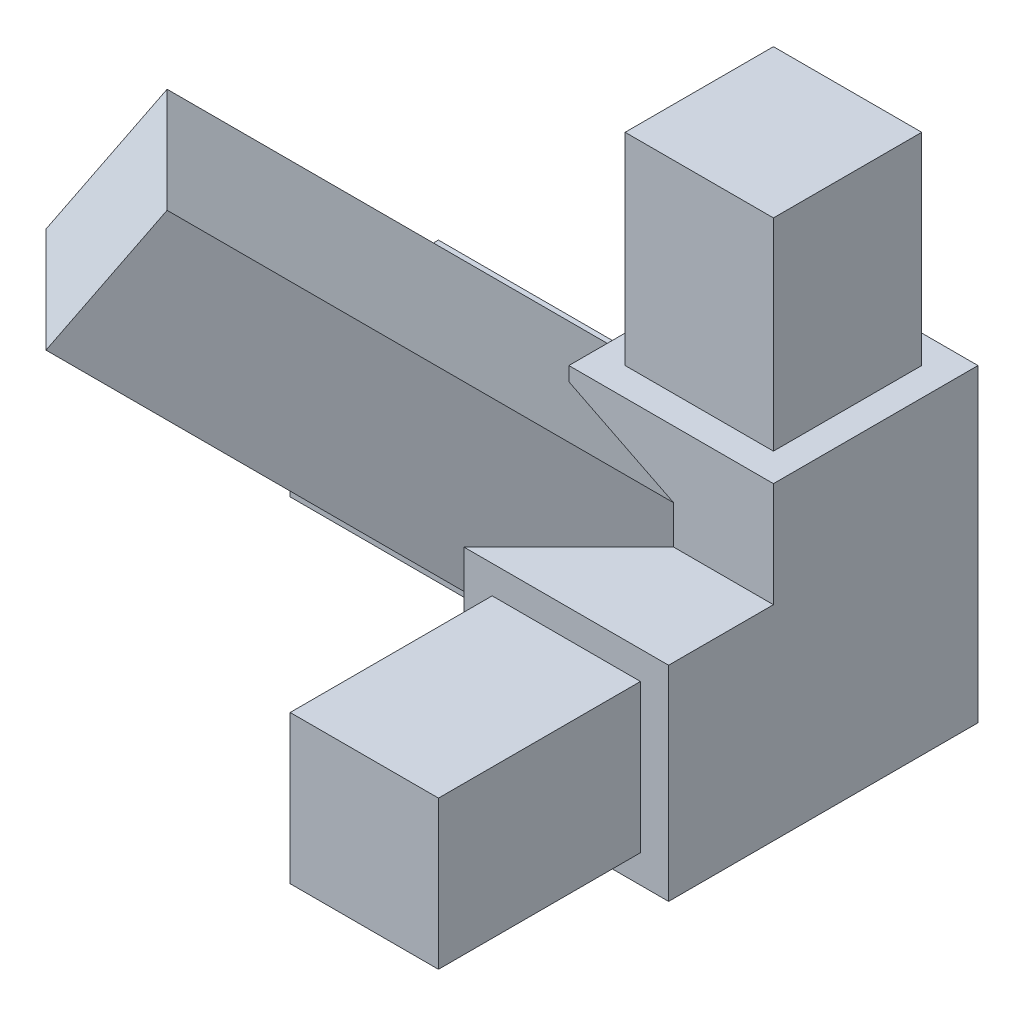
SolidWorks part; units mm, degrees
ref_plane "Front Plane" through (0, 0, 0) normal (0, 0, 1) x (1, 0, 0)
ref_plane "Top Plane" through (0, 0, 0) normal (0, 1, 0) x (1, 0, 0)
ref_plane "Right Plane" through (0, 0, 0) normal (1, 0, 0) x (0, 0, -1)
sketch "Sketch1" plane through (0, 0, 0) normal (0, 1, 0) x (1, 0, 0)
  line L1 (-4, -4) -> (4, -4)
  line L2 (-4, -4) -> (-4, 4)
  line L3 (-4, 4) -> (4, 4)
  line L4 (4, -4) -> (4, 4)
  point P4 (0, -4)
  point P5 (-4, 0)
  dimension "D1" = 8
extrude "Boss-Extrude1" add sketch "Sketch1" along normal mid plane 8
sketch "Sketch3" plane through (0, 0, 4) normal (0, 0, 1) x (1, 0, 0)
  line L1 (-2.9, 2.9) -> (2.9, 2.9)
  line L2 (-2.9, 2.9) -> (-2.9, -2.9)
  line L3 (-2.9, -2.9) -> (2.9, -2.9)
  line L4 (2.9, 2.9) -> (2.9, -2.9)
  line L5 (-2.9, 2.9) -> (2.9, -2.9) construction
  line L6 (-2.9, -2.9) -> (2.9, 2.9) construction
  point P0 (0, 0)
  dimension "D1" = 5.8
extrude "Boss-Extrude2" add sketch "Sketch3" along normal blind 12
sketch "Sketch5" plane through (0, 4, 0) normal (0, 1, 0) x (1, 0, 0)
  line L1 (-2.9, 2.9) -> (2.9, 2.9)
  line L2 (-2.9, 2.9) -> (-2.9, -2.9)
  line L3 (-2.9, -2.9) -> (2.9, -2.9)
  line L4 (2.9, 2.9) -> (2.9, -2.9)
  line L5 (-2.9, 2.9) -> (2.9, -2.9) construction
  line L6 (-2.9, -2.9) -> (2.9, 2.9) construction
  point P0 (0, 0)
  dimension "D1" = 5.8
extrude "Boss-Extrude3" add sketch "Sketch5" along normal blind 12
sketch "Sketch6" plane through (-4, 0, 0) normal (-1, 0, 0) x (0, 0, 1)
  line L1 (2.9, -2.9) -> (-2.9, -2.9)
  line L2 (2.9, -2.9) -> (2.9, 2.9)
  line L3 (2.9, 2.9) -> (-2.9, 2.9)
  line L4 (-2.9, -2.9) -> (-2.9, 2.9)
  line L5 (2.9, -2.9) -> (-2.9, 2.9) construction
  line L6 (2.9, 2.9) -> (-2.9, -2.9) construction
  point P0 (0, 0)
  dimension "D1" = 5.8
extrude "Boss-Extrude4" add sketch "Sketch6" along normal blind 12
ref_plane "Plane2" through (-7.2667, 7.2667, 7.2667) normal (0.5774, -0.5774, -0.5774) x (-0.8165, -0.4082, -0.4082)
sketch "Sketch8" plane through (-7.2667, 7.2667, 7.2667) normal (0.5774, -0.5774, -0.5774) x (-0.8165, -0.4082, -0.4082)
  line L1 (1.0615, 3.9615) -> (-3.9615, 1.0615)
  line L2 (1.0615, 3.9615) -> (3.9615, -1.0615)
  line L3 (3.9615, -1.0615) -> (-1.0615, -3.9615)
  line L4 (-3.9615, 1.0615) -> (-1.0615, -3.9615)
  line L5 (1.0615, 3.9615) -> (-1.0615, -3.9615) construction
  line L6 (3.9615, -1.0615) -> (-3.9615, 1.0615) construction
  line L8 (10.6961, 0) -> (-5.3481, -9.2631) construction
  point P0 (0, 0)
  dimension "D1" = 5.8
extrude "Boss-Extrude5" add sketch "Sketch8" along normal up to next and the other way blind 10
sketch "Sketch9" plane through (-4, 0, 0) normal (-1, 0, 0) x (0, 0, 1)
  line L1 (4, -4) -> (-4, -4)
  line L2 (4, -4) -> (4, 4)
  line L3 (4, 4) -> (-4, 4)
  line L4 (-4, -4) -> (-4, 4)
  line L5 (4, -4) -> (-4, 4) construction
  line L6 (4, 4) -> (-4, -4) construction
  point P0 (0, 0)
extrude "Boss-Extrude6" add sketch "Sketch9" along normal blind 4.1
sketch "Sketch10" plane through (0, 0, 4) normal (0, 0, 1) x (1, 0, 0)
  line L1 (-4, -4) -> (4, -4)
  line L2 (-4, -4) -> (-4, 4)
  line L3 (-4, 4) -> (4, 4)
  line L4 (4, -4) -> (4, 4)
  line L5 (-4, -4) -> (4, 4) construction
  line L6 (-4, 4) -> (4, -4) construction
  point P0 (0, 0)
extrude "Boss-Extrude7" add sketch "Sketch10" along normal blind 4.1
sketch "Sketch11" plane through (0, 4, 0) normal (0, 1, 0) x (1, 0, 0)
  line L1 (-4, -4) -> (4, -4)
  line L2 (-4, -4) -> (-4, 4)
  line L3 (-4, 4) -> (4, 4)
  line L4 (4, -4) -> (4, 4)
  line L5 (-4, -4) -> (4, 4) construction
  line L6 (-4, 4) -> (4, -4) construction
  point P0 (0, 0)
extrude "Boss-Extrude8" add sketch "Sketch11" along normal blind 4.1
